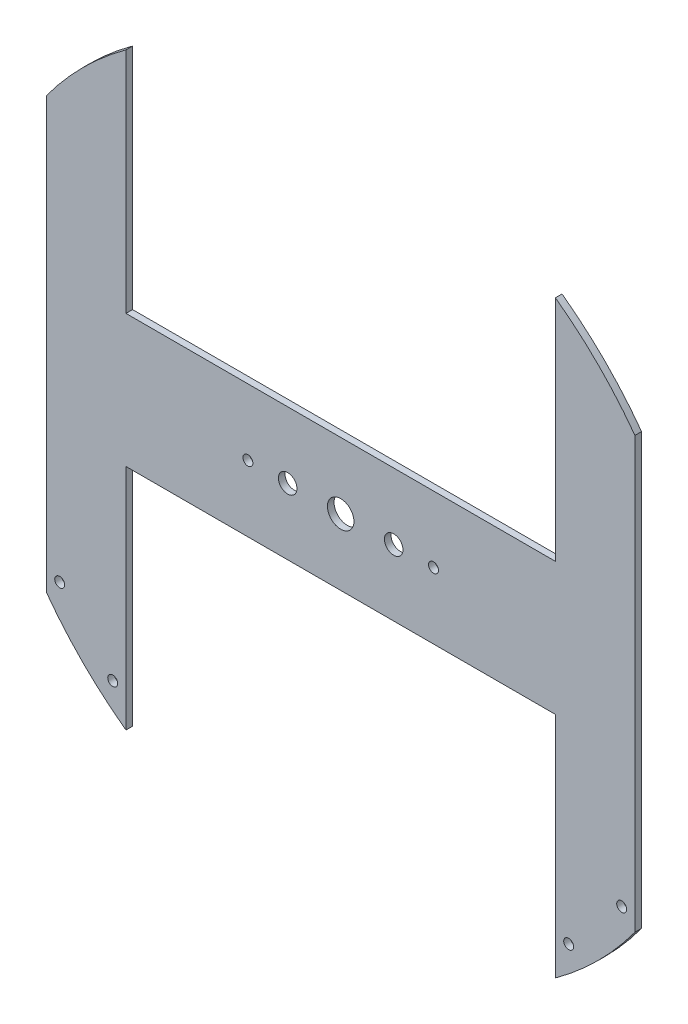
SolidWorks part; units mm, degrees
material "6061 Alloy"
ref_plane "Front Plane" through (0, 0, 0) normal (0, 0, 1) x (1, 0, 0)
ref_plane "Top Plane" through (0, 0, 0) normal (0, 1, 0) x (1, 0, 0)
ref_plane "Right Plane" through (0, 0, 0) normal (1, 0, 0) x (0, 0, -1)
sketch "Sketch1" plane through (0, 0, 0) normal (0, 0, 1) x (1, 0, 0)
  line L1 (-140.9655, 145.0225) -> (-102.8655, 145.0225)
  line L2 (-140.9655, 145.0225) -> (-140.9655, -145.0225)
  line L3 (-140.9655, -145.0225) -> (-102.8655, -145.0225)
  line L4 (-102.8655, 145.0225) -> (-102.8655, -145.0225)
  line L5 (-140.9655, 145.0225) -> (-102.8655, -145.0225) construction
  line L6 (-140.9655, -145.0225) -> (-102.8655, 145.0225) construction
  line L7 (-140.9655, 31.75) -> (140.9655, 31.75)
  line L8 (-140.9655, 31.75) -> (-140.9655, -31.75)
  line L9 (-140.9655, -31.75) -> (140.9655, -31.75)
  line L10 (140.9655, 31.75) -> (140.9655, -31.75)
  line L11 (-140.9655, 31.75) -> (140.9655, -31.75) construction
  line L12 (-140.9655, -31.75) -> (140.9655, 31.75) construction
  line L13 (102.8655, 145.0225) -> (140.9655, 145.0225)
  line L14 (102.8655, 145.0225) -> (102.8655, -145.0225)
  line L15 (102.8655, -145.0225) -> (140.9655, -145.0225)
  line L16 (140.9655, 145.0225) -> (140.9655, -145.0225)
  line L17 (102.8655, 145.0225) -> (140.9655, -145.0225) construction
  line L18 (102.8655, -145.0225) -> (140.9655, 145.0225) construction
  circle A0 centre (0, 0) radius 177.8
  circle A1 centre (25.4, 0) radius 4.445
  circle A2 centre (-25.4, 0) radius 4.445
  circle A3 centre (0, 0) radius 25.4 construction
  circle A4 centre (-44.45, 0) radius 2.3812
  circle A5 centre (44.45, 0) radius 2.3812
  point P3 (-121.9155, 0)
  point P12 (121.9155, 0)
  dimension "D1" = 355.6
  dimension "D5" = 50.8
  dimension "D6" = 8.89
  dimension "D7" = 8.89
  dimension "D10" = 4.7625
  dimension "D11" = 4.7625
  dimension "D2" = 38.1
  dimension "D3" = 38.1
  dimension "D4" = 63.5
  dimension "D8" = 44.45
  dimension "D9" = 44.45
extrude "Boss-Extrude1" add sketch "Sketch1" along normal blind 3.175 contours L4 A0 L2 L7 | L2 L9 L4 L7 | L14 L7 L4 L9 A2 A1 | L2 A0 L4 L9 | L16 A0 L14 L7 | L7 L14 L9 L10 | L14 A0 L16 L9 region at (-120.723, 80.7079, 0) region at (0, 0, 0) region at (-121.9155, 0, 0) region at (120.723, 80.7079, 0) region at (-120.723, -80.7079, 0) region at (121.9155, 0, 0) region at (120.723, -80.7079, 0)
sketch "Sketch2" plane through (0, 0, 3.175) normal (0, 0, 1) x (1, 0, 0)
  line L0 (-140.9655, -103.066) -> (-140.9655, -108.3585)
  line L1 (-140.9655, 108.3585) -> (-140.9655, -108.3585) construction
  line L2 (-102.8655, -141.1119) -> (-102.8655, -145.0225)
  line L3 (102.8655, -141.1119) -> (102.8655, -145.0225)
  line L4 (102.8655, -31.75) -> (102.8655, -145.0225) construction
  line L5 (140.9655, -103.066) -> (140.9655, -108.3585)
  line L6 (140.9655, 108.3585) -> (140.9655, -108.3585) construction
  line L7 (-102.8655, -31.75) -> (-102.8655, -145.0225) construction
  circle A0 centre (0, 0) radius 177.8
  circle A1 centre (0, 0) radius 174.625
  line M3 (-140.9655, 108.3585) -> (-140.9655, -108.3585)
  arc M4 (-140.9655, -108.3585) -> (-102.8655, -145.0225) centre (0, 0) ccw
  line M5 (-102.8655, -145.0225) -> (-102.8655, -31.75)
  line M7 (102.8655, -31.75) -> (102.8655, -145.0225)
  arc M8 (102.8655, -145.0225) -> (140.9655, -108.3585) centre (0, 0) ccw
  line M9 (140.9655, -108.3585) -> (140.9655, 108.3585)
  dimension "D1" = 355.6
  dimension "D2" = 349.25
extrude "Boss-Extrude2" add sketch "Sketch2" along normal blind 50.8 contours A1 M3 M4 M5 | A1 M7 M8 M9 region at (-122.8631, -125.3578, 3.175) region at (122.8631, -125.3578, 3.175)
sketch "Sketch3" plane through (0, 0, 3.175) normal (0, 0, 1) x (1, 0, 0)
  circle A0 centre (0, 0) radius 174.625
  circle A1 centre (0, 0) radius 203.8293
  dimension "D1" = 349.25
extrude "Cut-Extrude1" cut sketch "Sketch3" along normal through all and the other way through all
sketch "Sketch4" plane through (0, 0, 3.175) normal (0, 0, 1) x (1, 0, 0)
  circle A0 centre (0, 0) radius 6.35
  dimension "D1" = 12.7
extrude "Cut-Extrude2" cut sketch "Sketch4" against normal through all
sketch "Sketch5" plane through (0, 0, 3.175) normal (0, 0, 1) x (1, 0, 0)
  line L0 (0, 165.1) -> (0, -165.1) construction
  line L1 (102.8655, -31.75) -> (102.8655, -141.1119) construction
  circle A0 centre (0, 0) radius 165.1 construction
  circle A1 centre (134.6155, -95.5859) radius 2.3813
  circle A2 centre (109.2155, -123.8143) radius 2.3813
  circle A3 centre (-134.6155, -95.5859) radius 2.3813
  circle A4 centre (-109.2155, -123.8143) radius 2.3813
  point P9 (111.7068, -121.5714)
  dimension "D1" = 330.2
  dimension "D3" = 4.7625
  dimension "D4" = 4.7625
  dimension "D2" = 25.4
  dimension "D5" = 6.35
extrude "Cut-Extrude3" cut sketch "Sketch5" against normal through all
